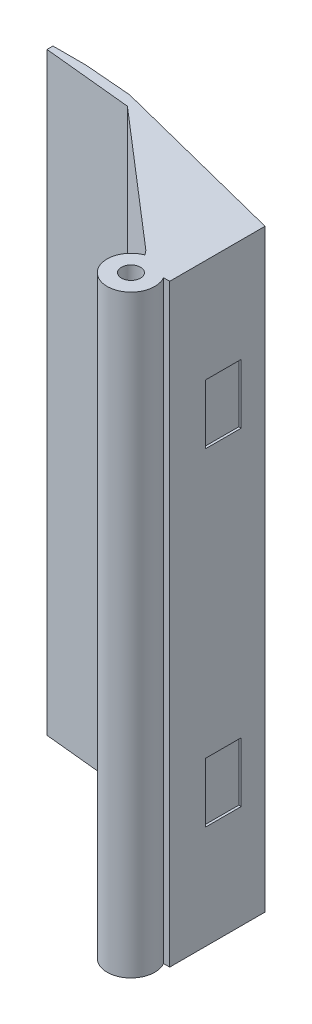
SolidWorks part; units mm, degrees
ref_plane "前视基准面" through (0, 0, 0) normal (0, 0, 1) x (1, 0, 0)
ref_plane "上视基准面" through (0, 0, 0) normal (0, 1, 0) x (1, 0, 0)
ref_plane "右视基准面" through (0, 0, 0) normal (1, 0, 0) x (0, 0, -1)
other "Configuration Table"
sketch "草图1" plane through (0, 0, 0) normal (0, 1, 0) x (1, 0, 0)
  line L0 (-198, -1.2) -> (-198, -3.2)
  line L1 (-198, -3.2) -> (-168, -6.2)
  line L2 (-168, -6.2) -> (-123, -45)
  line L3 (-123, -45) -> (-119, -50)
  line L4 (-119, -50) -> (-110, -50)
  line L5 (-110, -50) -> (-110, -18)
  line L6 (-110, -18) -> (-171, -2.5)
  line L7 (-171, -2.5) -> (-187, -1.2)
  line L8 (-187, -1.2) -> (-198, -1.2)
extrude "One_piece_progressive_solid_wedge" add sketch "草图1" along normal blind 99.7 and the other way blind 99.7
sketch "草图2" plane through (0, 0, 0) normal (0, 1, 0) x (1, 0, 0)
  circle A0 centre (-119, -54) radius 8
extrude "Integral_full_width_pivot_boss" add sketch "草图2" along normal blind 99.7 and the other way blind 99.7
sketch "草图3" plane through (0, 0, 0) normal (0, 1, 0) x (1, 0, 0)
  circle A0 centre (-119, -54) radius 3.2
extrude "M6_manual_pivot" cut sketch "草图3" against normal blind 110 and the other way blind 110
sketch "草图4" plane through (0, 0, 0) normal (0, 1, 0) x (1, 0, 0)
  line L1 (-110.8, -38) -> (-109.99, -38)
  line L2 (-110.8, -38) -> (-110.8, -26)
  line L3 (-110.8, -26) -> (-109.99, -26)
  line L4 (-109.99, -38) -> (-109.99, -26)
extrude "Recessed_hook_patch_-65" cut sketch "草图4" against normal blind 20 from offset 45 offset against normal yes
sketch "草图5" plane through (0, 0, 0) normal (0, 1, 0) x (1, 0, 0)
  line L1 (-110.8, -38) -> (-109.99, -38)
  line L2 (-110.8, -38) -> (-110.8, -26)
  line L3 (-110.8, -26) -> (-109.99, -26)
  line L4 (-109.99, -38) -> (-109.99, -26)
extrude "Recessed_hook_patch_45" cut sketch "草图5" against normal blind 20 from offset 65
